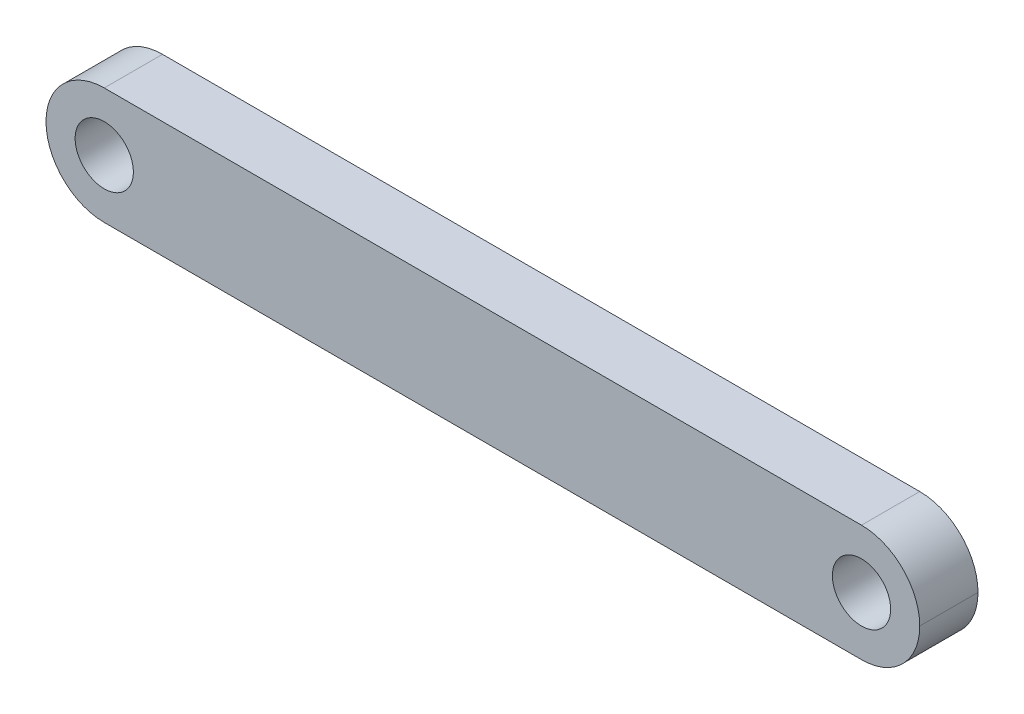
SolidWorks part; units mm, degrees
ref_plane "Front Plane" through (0, 0, 0) normal (0, 0, 1) x (1, 0, 0)
ref_plane "Top Plane" through (0, 0, 0) normal (0, 1, 0) x (1, 0, 0)
ref_plane "Right Plane" through (0, 0, 0) normal (1, 0, 0) x (0, 0, -1)
sketch "Sketch1" plane through (0, 0, 0) normal (0, 0, 1) x (1, 0, 0)
  line L1 (0, 0) -> (150, 0)
  line L2 (0, 0) -> (0, 20)
  line L3 (0, 20) -> (150, 20)
  line L4 (150, 0) -> (150, 20)
  dimension "D1" = 20
  dimension "D2" = 150
extrude "Boss-Extrude1" add sketch "Sketch1" along normal blind 10
fillet "Fillet1" radius 10 4 edges at (0, 0, 5) (150, 0, 5) (150, 20, 5) (0, 20, 5)
sketch "Sketch2" plane through (0, 0, 10) normal (0, 0, 1) x (1, 0, 0)
  circle A0 centre (10, 10) radius 5
  circle A1 centre (140, 10) radius 5
  arc A2 (10, 20) -> (0, 10) centre (10, 10) ccw construction
  arc A3 (150, 10) -> (140, 20) centre (140, 10) ccw construction
  dimension "D1" = 10
extrude "Cut-Extrude1" cut sketch "Sketch2" against normal through all
